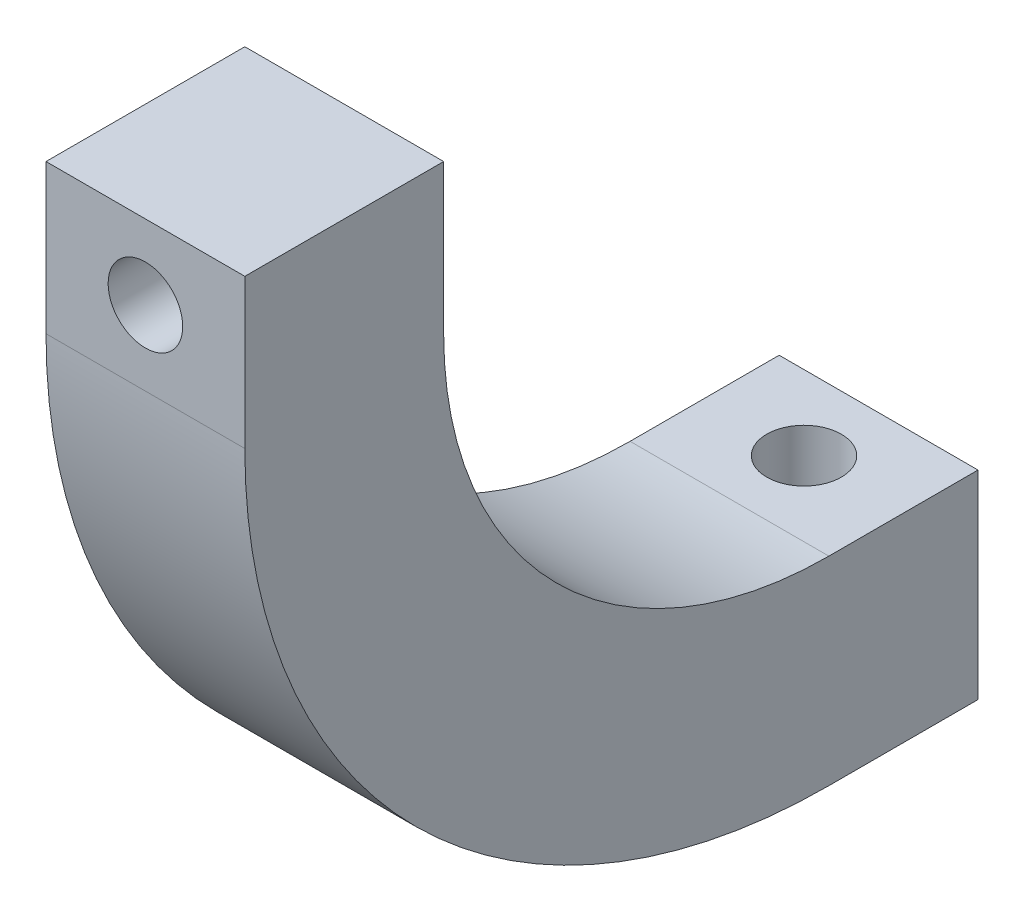
SolidWorks part; units mm, degrees
ref_plane "Front Plane" through (0, 0, 0) normal (0, 0, 1) x (1, 0, 0)
ref_plane "Top Plane" through (0, 0, 0) normal (0, 1, 0) x (1, 0, 0)
ref_plane "Right Plane" through (0, 0, 0) normal (1, 0, 0) x (0, 0, -1)
ref_axis "Z" through (0, 0, 22.75) along (0, 0, -1)
sketch "Sketch4" plane through (0, 0, 0) normal (0, 0, 1) x (1, 0, 0)
  circle A0 centre (0, 0) radius 17.5 construction
  dimension "D1" = 35
sketch "Sketch5" plane through (0, 0, 0) normal (1, 0, 0) x (0, 0, -1)
  line L0 (-18.5, 3) -> (-18.5, 0)
  line L1 (-18.5, 0) -> (-18.5, -3)
  line L2 (-26.5, -3) -> (-26.5, 3)
  line L6 (-26.5, 3) -> (-18.5, 3)
  line L12 (-22.75, 0) -> (-13.0351, 0) construction
  line L13 (0, 0) -> (-14.9091, -14.9091) construction
  line L14 (0, 0) -> (7.0065, 0) construction
  line L15 (0, -18.5) -> (-3, -18.5)
  line L16 (3, -18.5) -> (0, -18.5)
  line L17 (-3, -26.5) -> (3, -26.5)
  line L18 (3, -26.5) -> (3, -18.5)
  circle A0 centre (0, 0) radius 14 construction
  arc A1 (-18.5, -3) -> (-3, -18.5) centre (-3, -3) ccw
  arc A2 (-26.5, -3) -> (-3, -26.5) centre (-3, -3) ccw
  point P2 (9.4307, -21)
  point P4 (0, -2.1363)
  dimension "D1" = 28
  dimension "D4" = 3
  dimension "D2" = 45
  dimension "D3" = 8
  dimension "D5" = 18.5
sketch "Sketch6" plane through (0, 0, 0) normal (0, 1, 0) x (1, 0, 0)
  circle A0 centre (0, 0) radius 17.5 construction
  dimension "D1" = 35
extrude "Boss-Extrude1" add sketch "Sketch5" along normal blind 4 and the other way blind 4
sketch "Sketch7" plane through (0, 0, 0) normal (0, 0, 1) x (1, 0, 0)
  circle A0 centre (0, 0) radius 1.5
  dimension "D1" = 3
extrude "Cut-Extrude1" cut sketch "Sketch7" along normal through all
sketch "Sketch8" plane through (0, 0, 0) normal (0, 1, 0) x (1, 0, 0)
  circle A0 centre (0, 0) radius 1.5
  dimension "D1" = 3
extrude "Cut-Extrude2" cut sketch "Sketch8" against normal through all
ref_axis "Y" through (0, -9.3489, 0) along (0, -1, 0)
equation "\"rbracket-width\"= \"L2Thickness\""
equation "\"EyeCaptureRadius\"= ( \"EyeDiameter\" + \"EyeClearance\" ) / 2"
equation "\"rbracket_planetocenterline_dist\"= \"BasePlaneDistance\""
equation "\"EyeDiameter\" = 35"
equation "\"BasePlaneDistance\" = \"EyeDiameter\"/2+19.84"
equation "\"EyeClearance\" = 2"
equation "\"D1@Sketch4\"=\"EyeDiameter\""
equation "\"D1@Sketch6\"=\"EyeDiameter\""
equation "\"D1@Boss-Extrude1\"=\"rbracket-width\"/2"
equation "\"D2@Boss-Extrude1\"=\"rbracket-width\"/2"
equation "\"L2Thickness\" = 8"
equation "\"D3@Sketch5\"=\"L2Thickness\""
equation "\"D5@Sketch5\"=(\"EyeDiameter\"+\"EyeClearance\")/2"
